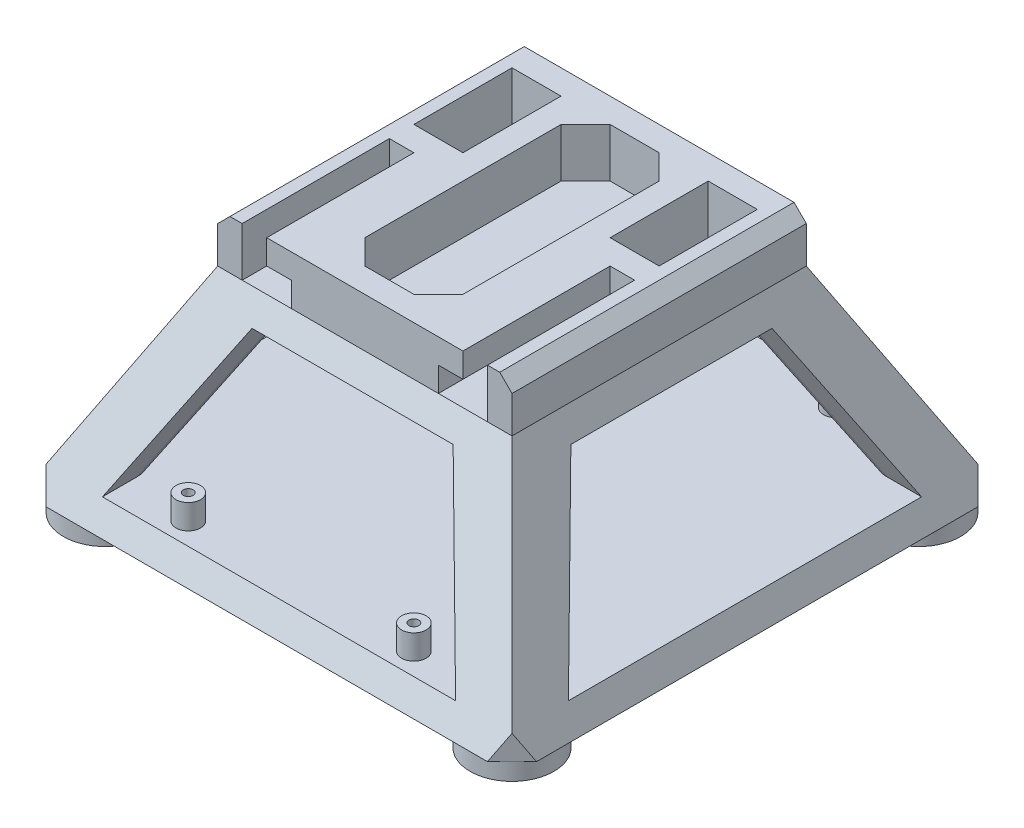
SolidWorks part; units mm, degrees
material "9400A光敏树脂"
ref_plane "前视基准面" through (0, 0, 0) normal (0, 0, 1) x (1, 0, 0)
ref_plane "上视基准面" through (0, 0, 0) normal (0, 1, 0) x (1, 0, 0)
ref_plane "右视基准面" through (0, 0, 0) normal (1, 0, 0) x (0, 0, -1)
other "Configuration Table"
sketch "草图1" plane through (0, 0, 0) normal (0, 1, 0) x (1, 0, 0)
  line L1 (-50, 50) -> (50, 50)
  line L2 (-50, 50) -> (-50, -50)
  line L3 (-50, -50) -> (50, -50)
  line L4 (50, 50) -> (50, -50)
  line L5 (-50, 50) -> (50, -50) construction
  line L6 (-50, -50) -> (50, 50) construction
  point P0 (0, 0)
  dimension "D1" = 100
  dimension "D2" = 100
ref_plane "基准面1" through (0, 40, 0) normal (0, 1, 0) x (1, 0, 0)
sketch "草图2" plane through (0, 40, 0) normal (0, 1, 0) x (1, 0, 0)
  line L1 (-30, 30) -> (30, 30)
  line L2 (-30, 30) -> (-30, -30)
  line L3 (-30, -30) -> (30, -30)
  line L4 (30, 30) -> (30, -30)
  line L5 (-30, 30) -> (30, -30) construction
  line L6 (-30, -30) -> (30, 30) construction
  point P0 (0, 0)
  dimension "D1" = 60
  dimension "D2" = 60
loft "放样1" add profiles "草图1", "草图2" connector at (-50, 0, 50) connector at (-30, 40, 30)
ref_plane "基准面2" through (0, 5, 0) normal (0, 1, 0) x (1, 0, 0)
sketch "草图4" plane through (0, 5, 0) normal (0, 1, 0) x (1, 0, 0)
  line L0 (50, 50) -> (30, 30) construction
  line L1 (-48, -48) -> (48, -48) construction
  line L2 (-48, -48) -> (-48, 48) construction
  line L3 (-48, 48) -> (48, 48) construction
  line L4 (48, -48) -> (48, 48) construction
  line L5 (-48, -48) -> (48, 48) construction
  line L6 (-48, 48) -> (48, -48) construction
  line L7 (-36, -48) -> (36, -48)
  line L8 (-48, 48) -> (-36, 48) construction
  line L9 (-48, 48) -> (-48, 36) construction
  line L10 (-48, 36) -> (-36, 36)
  line L11 (-36, 48) -> (-36, 36)
  line L12 (-48, -48) -> (-36, -48) construction
  line L13 (-48, -48) -> (-48, -36) construction
  line L14 (-48, -36) -> (-36, -36)
  line L15 (-36, -48) -> (-36, -36)
  line L16 (48, -48) -> (36, -48) construction
  line L17 (48, -48) -> (48, -36) construction
  line L18 (48, -36) -> (36, -36)
  line L19 (36, -48) -> (36, -36)
  line L20 (48, 48) -> (36, 48) construction
  line L21 (48, 48) -> (48, 36) construction
  line L22 (48, 36) -> (36, 36)
  line L23 (36, 48) -> (36, 36)
  line L24 (48, -36) -> (48, 36)
  line L25 (36, 48) -> (-36, 48)
  line L26 (-48, -36) -> (-48, 36)
  point P0 (0, 0)
  dimension "D1" = 96
  dimension "D2" = 12
  dimension "D3" = 12
  dimension "D4" = 12
  dimension "D5" = 12
ref_plane "基准面3" through (0, 35, 0) normal (0, 1, 0) x (1, 0, 0)
sketch "草图6" plane through (0, 35, 0) normal (0, 1, 0) x (1, 0, 0)
  line L0 (-48, -48) -> (48, 48) construction
  line L1 (-32.5, -32.5) -> (32.5, -32.5) construction
  line L2 (-32.5, -32.5) -> (-32.5, 32.5) construction
  line L3 (-32.5, 32.5) -> (32.5, 32.5) construction
  line L4 (32.5, -32.5) -> (32.5, 32.5) construction
  line L5 (-32.5, -32.5) -> (32.5, 32.5) construction
  line L6 (-32.5, 32.5) -> (32.5, -32.5) construction
  line L7 (-32.5, 20.5) -> (-32.5, -20.5)
  line L8 (-32.5, 32.5) -> (-20.5, 32.5) construction
  line L9 (-32.5, 32.5) -> (-32.5, 20.5) construction
  line L10 (-32.5, 20.5) -> (-20.5, 20.5)
  line L11 (-20.5, 32.5) -> (-20.5, 20.5)
  line L12 (-32.5, -32.5) -> (-20.5, -32.5) construction
  line L13 (-32.5, -32.5) -> (-32.5, -20.5) construction
  line L14 (-32.5, -20.5) -> (-20.5, -20.5)
  line L15 (-20.5, -32.5) -> (-20.5, -20.5)
  line L16 (32.5, -32.5) -> (20.5, -32.5) construction
  line L17 (32.5, -32.5) -> (32.5, -20.5) construction
  line L18 (32.5, -20.5) -> (20.5, -20.5)
  line L19 (20.5, -32.5) -> (20.5, -20.5)
  line L20 (32.5, 32.5) -> (20.5, 32.5) construction
  line L21 (32.5, 32.5) -> (32.5, 20.5) construction
  line L22 (32.5, 20.5) -> (20.5, 20.5)
  line L23 (20.5, 32.5) -> (20.5, 20.5)
  line L24 (-20.5, -32.5) -> (20.5, -32.5)
  line L25 (32.5, -20.5) -> (32.5, 20.5)
  line L26 (20.5, 32.5) -> (-20.5, 32.5)
  point P0 (0, 0)
  dimension "D1" = 65
  dimension "D2" = 12
  dimension "D3" = 12
  dimension "D4" = 12
  dimension "D5" = 12
loft "切除-放样2" cut profiles "草图4", "草图6" connector at (-36, 5, -48) connector at (-20.5, 35, -32.5)
sketch "草图7" plane through (0, 0, 0) normal (0, 0, 1) x (1, 0, 0)
  line L0 (-10, 40) -> (10, 40) construction
  line L1 (-30, 40) -> (30, 40) construction
  line L2 (-10, 40) -> (-10, 50)
  line L3 (-10, 50) -> (-20, 50)
  line L4 (-20, 50) -> (-20, 45)
  line L5 (-20, 45) -> (-15, 45)
  line L6 (-15, 45) -> (-15, 40)
  line L7 (-15, 40) -> (-10, 40)
  line L8 (-30, 40) -> (-30, 50)
  line L9 (-30, 50) -> (-25, 50)
  line L10 (-25, 50) -> (-25, 40)
  line L11 (-25, 40) -> (-30, 40)
  line L12 (0, -1000) -> (0, 49000) construction
  line L13 (25, 40) -> (30, 40)
  line L14 (25, 50) -> (25, 40)
  line L15 (30, 50) -> (25, 50)
  line L16 (30, 40) -> (30, 50)
  line L17 (15, 40) -> (10, 40)
  line L18 (15, 45) -> (15, 40)
  line L19 (20, 45) -> (15, 45)
  line L20 (20, 50) -> (20, 45)
  line L21 (10, 50) -> (20, 50)
  line L22 (10, 40) -> (10, 50)
  point P5 (0, 40)
  dimension "D1" = 20
  dimension "D2" = 10
  dimension "D3" = 10
  dimension "D4" = 5
  dimension "D5" = 5
  dimension "D6" = 10
  dimension "D7" = 5
extrude "凸台-拉伸1" add sketch "草图7" along normal blind 30 and the other way blind 30
sketch "草图8" plane through (0, 0, 0) normal (0, 1, 0) x (1, 0, 0)
  line L0 (-50, 50) -> (-45, 50)
  line L1 (50, 50) -> (-50, 50) construction
  line L2 (-45, 50) -> (-50, 45)
  line L3 (-50, 50) -> (-50, -50) construction
  line L4 (-50, 45) -> (-50, 50)
  line L5 (45, 50) -> (50, 50)
  line L6 (50, 50) -> (50, 45)
  line L7 (50, -50) -> (50, 50) construction
  line L8 (45, 50) -> (50, 45)
  line L9 (-50, -50) -> (-45, -50)
  line L10 (-50, -50) -> (50, -50) construction
  line L11 (-45, -50) -> (-50, -45)
  line L12 (-50, -45) -> (-50, -50)
  line L13 (50, -50) -> (50, -45)
  line L14 (50, -45) -> (45, -50)
  line L15 (45, -50) -> (50, -50)
  dimension "D1" = 5
  dimension "D2" = 5
  dimension "D3" = 5
  dimension "D4" = 5
  dimension "D5" = 5
  dimension "D6" = 5
  dimension "D7" = 5
  dimension "D8" = 5
extrude "切除-拉伸1" cut sketch "草图8" along normal through all
sketch "草图10" plane through (0, 0, 0) normal (0, 0, 1) x (1, 0, 0)
  line L0 (-30, 50) -> (-27.5, 50)
  line L1 (-25, 50) -> (-30, 50) construction
  line L2 (-27.5, 50) -> (-30, 47.5)
  line L3 (-30, 50) -> (-30, 40) construction
  line L4 (-30, 47.5) -> (-30, 50)
  line L5 (0, -1000) -> (0, 49000) construction
  line L6 (30, 47.5) -> (30, 50)
  line L7 (27.5, 50) -> (30, 47.5)
  line L8 (30, 50) -> (27.5, 50)
  dimension "D1" = 2.5
extrude "切除-拉伸3" cut sketch "草图10" along normal up to surface (30 mm away) from surface up to face at (-15.4167, 44.5833, 30) starting at face at (-15.4167, 44.5833, -30)
sketch "草图12" plane through (0, 0, 0) normal (0, 0, 1) x (1, 0, 0)
  line L1 (-15, 40) -> (-25, 40)
  line L2 (-15, 40) -> (-15, 50)
  line L3 (-15, 50) -> (-25, 50)
  line L4 (-25, 40) -> (-25, 50)
  line L5 (15, 40) -> (25, 40)
  line L6 (15, 40) -> (15, 50)
  line L7 (15, 50) -> (25, 50)
  line L8 (25, 40) -> (25, 50)
extrude "凸台-拉伸3" add sketch "草图12" against normal blind 5
sketch "草图13" plane through (0, 0, 0) normal (0, 0, 1) x (1, 0, 0)
  line L1 (25, 50) -> (15, 50)
  line L2 (25, 50) -> (25, 40)
  line L3 (25, 40) -> (15, 40)
  line L4 (15, 50) -> (15, 40)
  line L5 (-25, 50) -> (-15, 50)
  line L6 (-25, 50) -> (-25, 40)
  line L7 (-25, 40) -> (-15, 40)
  line L8 (-15, 50) -> (-15, 40)
extrude "凸台-拉伸4" add sketch "草图13" along normal blind 5 from surface starting at face at (14.5833, 45.4167, -30)
sketch "草图14" plane through (0, 0, 0) normal (0, 0, 1) x (1, 0, 0)
  line L1 (-10, 50) -> (10, 50)
  line L2 (-10, 50) -> (-10, 40)
  line L3 (-10, 40) -> (10, 40)
  line L4 (10, 50) -> (10, 40)
extrude "凸台-拉伸5" add sketch "草图14" against normal blind 5 from surface starting at face at (14.5833, 45.4167, 30)
sketch "草图15" plane through (0, 0, 0) normal (0, 1, 0) x (1, 0, 0)
  line L0 (0, -1000) -> (0, 49000) construction
  line L1 (20, 5) -> (15, 5)
  line L2 (20, 5) -> (20, 25)
  line L3 (20, 25) -> (15, 25)
  line L4 (15, 5) -> (15, 25)
  line L5 (-20, 5) -> (-15, 5)
  line L6 (-15, 5) -> (-15, 25)
  line L7 (-20, 25) -> (-15, 25)
  line L8 (-20, 5) -> (-20, 25)
  dimension "D1" = 20
  dimension "D2" = 5
extrude "切除-拉伸4" cut sketch "草图15" against normal blind 5 from surface starting at face at (-22.5, 50, -15)
sketch "草图16" plane through (0, 0, 0) normal (0, 0, 1) x (1, 0, 0)
  line L1 (10, 50) -> (-10, 50)
  line L2 (10, 50) -> (10, 40)
  line L3 (10, 40) -> (-10, 40)
  line L4 (-10, 50) -> (-10, 40)
extrude "凸台-拉伸6" add sketch "草图16" along normal blind 5 from surface starting at face at (21.7857, 44.1071, -30)
sketch "草图18" plane through (0, 0, 0) normal (0, 1, 0) x (1, 0, 0)
  line L0 (5, 25) -> (10, 25)
  line L1 (10, 25) -> (-10, 25) construction
  line L2 (10, 25) -> (10, 20)
  line L3 (10, 25) -> (10, -25) construction
  line L4 (10, 20) -> (5, 25)
  line L5 (-10, 25) -> (-5, 25)
  line L6 (-5, 25) -> (-10, 20)
  line L7 (-10, 25) -> (-10, -25) construction
  line L8 (-10, 20) -> (-10, 25)
  line L9 (-10, -25) -> (-5, -25)
  line L10 (-10, -25) -> (10, -25) construction
  line L11 (-5, -25) -> (-10, -20)
  line L12 (-10, -20) -> (-10, -25)
  line L14 (5, -25) -> (10, -25)
  line L15 (10, -25) -> (-10, -25) construction
  line L16 (10, -25) -> (10, -20)
  line L17 (10, -20) -> (5, -25)
  dimension "D1" = 5
  dimension "D2" = 5
  dimension "D3" = 5
  dimension "D4" = 5
  dimension "D5" = 5
  dimension "D6" = 5
  dimension "D7" = 5
  dimension "D8" = 5
extrude "凸台-拉伸7" add sketch "草图18" along normal up to surface (50 mm away) from surface up to face at (0, 50, 0) starting at face at (0, 40, -12.5)
sketch "草图21" plane through (0, 0, 0) normal (0, 1, 0) x (1, 0, 0)
  line L1 (-25, -45) -> (25, -45) construction
  line L2 (-25, -45) -> (-25, 45) construction
  line L3 (-25, 45) -> (25, 45) construction
  line L4 (25, -45) -> (25, 45) construction
  line L5 (-25, -45) -> (25, 45) construction
  line L6 (-25, 45) -> (25, -45) construction
  circle A0 centre (-23, 43) radius 2 construction
  circle A1 centre (-23, -43) radius 2 construction
  circle A2 centre (23, -43) radius 2 construction
  circle A3 centre (23, 43) radius 2 construction
  circle A4 centre (-23, 43) radius 1
  circle A5 centre (23, 43) radius 1
  circle A6 centre (-23, -43) radius 1
  circle A7 centre (23, -43) radius 1
  point P0 (0, 0)
  dimension "D3" = 4
  dimension "D4" = 4
  dimension "D5" = 4
  dimension "D6" = 4
  dimension "D7" = 2
  dimension "D8" = 2
  dimension "D9" = 2
  dimension "D10" = 2
  dimension "D1" = 90
  dimension "D2" = 50
extrude "切除-拉伸5" cut sketch "草图21" against normal up to surface from surface up to face at (0, 0, 0) starting at face at (0, 5, 0)
sketch "草图22" plane through (0, 0, 0) normal (0, 1, 0) x (1, 0, 0)
  circle A0 centre (-23, 43) radius 2.5
  circle A1 centre (23, 43) radius 1
  circle A2 centre (23, 43) radius 1
  circle A3 centre (-23, 43) radius 1
  circle A4 centre (-23, 43) radius 1
  circle A5 centre (23, -43) radius 1
  circle A6 centre (23, -43) radius 1
  circle A7 centre (-23, -43) radius 1
  circle A8 centre (-23, -43) radius 1
  circle A9 centre (23, 43) radius 2.5
  circle A10 centre (-23, -43) radius 2.5
  circle A11 centre (23, -43) radius 2.5
  dimension "D5" = 5
  dimension "D6" = 5
  dimension "D7" = 5
  dimension "D8" = 5
  dimension "D1" = 0
  dimension "D2" = 0
  dimension "D3" = 0
  dimension "D4" = 0
extrude "凸台-拉伸8" add sketch "草图22" along normal blind 5 from surface starting at face at (23, 5, -42)
sketch "草图23" plane through (0, 0, 0) normal (0, 1, 0) x (1, 0, 0)
  circle A0 centre (-23, -43) radius 1.75
  circle A1 centre (23, -43) radius 1.75
  circle A2 centre (-23, 43) radius 1.75
  circle A3 centre (23, 43) radius 1.75
  dimension "D1" = 3.5
  dimension "D2" = 3.5
  dimension "D3" = 3.5
  dimension "D4" = 3.5
extrude "切除-拉伸6" cut sketch "草图23" along normal blind 2
sketch "草图24" plane through (0, 0, 0) normal (0, 1, 0) x (1, 0, 0)
  line L0 (-45, -50) -> (-50, -45) construction
  line L1 (-50, 50) -> (50, 50) construction
  line L2 (-50, 50) -> (-50, -50) construction
  line L3 (-50, -50) -> (50, -50) construction
  line L4 (50, 50) -> (50, -50) construction
  line L5 (-50, 50) -> (50, -50) construction
  line L6 (-50, -50) -> (50, 50) construction
  line L7 (50, -45) -> (45, -50) construction
  line L9 (45, 50) -> (50, 45) construction
  line L10 (-50, 45) -> (-45, 50) construction
  line L11 (43.7626, 39.1664) -> (-39.1664, -43.7626) construction
  line L12 (-43.7626, -39.1664) -> (39.1664, 43.7626) construction
  line L13 (-39.1664, 43.7626) -> (43.7626, -39.1664) construction
  line L14 (39.1664, -43.7626) -> (-43.7626, 39.1664) construction
  line L15 (-39.1664, 43.7626) -> (-33.5855, 38.1817)
  line L16 (-43.7626, 39.1664) -> (-38.1817, 33.5855)
  line L17 (-38.1817, -33.5855) -> (-43.7626, -39.1664)
  line L18 (-33.5855, -38.1817) -> (-39.1664, -43.7626)
  line L19 (38.1817, -33.5855) -> (43.7626, -39.1664)
  line L20 (33.5855, -38.1817) -> (39.1664, -43.7626)
  line L21 (43.7626, 39.1664) -> (38.1817, 33.5855)
  line L22 (39.1664, 43.7626) -> (33.5855, 38.1817)
  arc A0 (33.5855, -38.1817) -> (38.1817, -33.5855) centre (41.4645, -41.4645) ccw
  arc A2 (38.1817, 33.5855) -> (33.5855, 38.1817) centre (41.4645, 41.4645) ccw
  arc A3 (-33.5855, 38.1817) -> (-38.1817, 33.5855) centre (-41.4645, 41.4645) ccw
  arc A4 (43.7626, 39.1664) -> (39.1664, 43.7626) centre (41.4645, 41.4645) ccw
  arc A5 (-38.1817, -33.5855) -> (-33.5855, -38.1817) centre (-41.4645, -41.4645) ccw
  arc A6 (-39.1664, 43.7626) -> (-43.7626, 39.1664) centre (-41.4645, 41.4645) ccw
  arc A7 (-43.7626, -39.1664) -> (-39.1664, -43.7626) centre (-41.4645, -41.4645) ccw
  arc A8 (39.1664, -43.7626) -> (43.7626, -39.1664) centre (41.4645, -41.4645) ccw
  point P0 (0, 0)
  dimension "D2" = 6.5
  dimension "D3" = 6.5
  dimension "D4" = 6.5
  dimension "D5" = 6.5
  dimension "D1" = 100
extrude "凸台-拉伸9" add sketch "草图24" against normal blind 3.5 from surface starting at face at (23, 0, 44.75)
sketch "草图25" plane through (0, 0, 0) normal (0, 1, 0) x (1, 0, 0)
  line L0 (-1000, 0) -> (49000, 0) construction
  line L1 (0, -1000) -> (0, 49000) construction
  line L2 (-42.5251, -40.4038) -> (-36.5835, -34.4622)
  line L3 (-40.4038, -42.5251) -> (-34.4622, -36.5835)
  line L4 (-50, 41.4645) -> (-50, -41.4645) construction
  line L5 (40.4038, -42.5251) -> (34.4622, -36.5835)
  line L6 (42.5251, -40.4038) -> (36.5835, -34.4622)
  line L7 (42.5251, 40.4038) -> (36.5835, 34.4622)
  line L8 (40.4038, 42.5251) -> (34.4622, 36.5835)
  line L9 (-40.4038, 42.5251) -> (-34.4622, 36.5835)
  line L10 (-42.5251, 40.4038) -> (-36.5835, 34.4622)
  arc A0 (-36.5835, -34.4622) -> (-34.4622, -36.5835) centre (-41.4645, -41.4645) ccw
  arc A4 (-42.5251, -40.4038) -> (-40.4038, -42.5251) centre (-41.4645, -41.4645) ccw
  arc A5 (42.5251, -40.4038) -> (40.4038, -42.5251) centre (41.4645, -41.4645) cw
  arc A6 (36.5835, -34.4622) -> (34.4622, -36.5835) centre (41.4645, -41.4645) cw
  arc A7 (36.5835, 34.4622) -> (34.4622, 36.5835) centre (41.4645, 41.4645) ccw
  arc A8 (42.5251, 40.4038) -> (40.4038, 42.5251) centre (41.4645, 41.4645) ccw
  arc A9 (-42.5251, 40.4038) -> (-40.4038, 42.5251) centre (-41.4645, 41.4645) cw
  arc A10 (-36.5835, 34.4622) -> (-34.4622, 36.5835) centre (-41.4645, 41.4645) cw
  dimension "D1" = 3
  dimension "D2" = 45
extrude "凸台-拉伸10" add sketch "草图25" along normal blind 2 from surface starting at face at (-42.1526, -3.5, -42.1526)
fillet "圆角1" radius 5 4 edges
